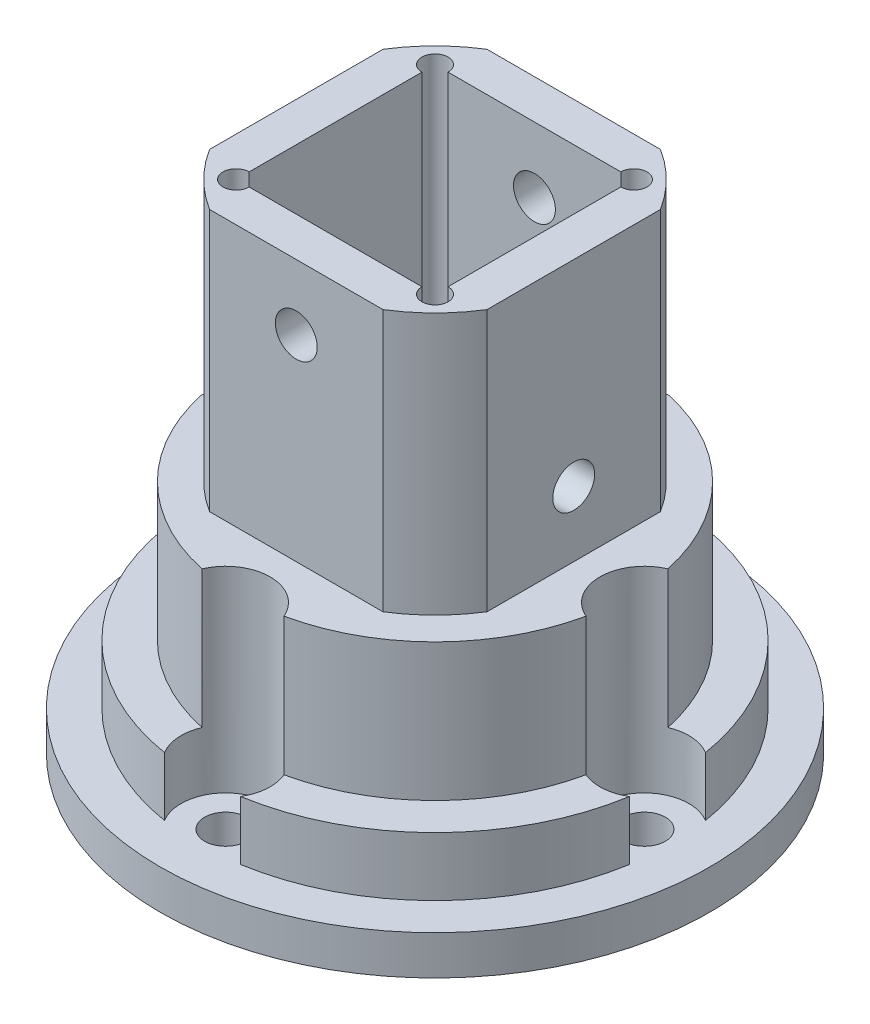
SolidWorks part; units mm, degrees
ref_plane "前视基准面" through (0, 0, 0) normal (0, 0, 1) x (1, 0, 0)
ref_plane "上视基准面" through (0, 0, 0) normal (0, 1, 0) x (1, 0, 0)
ref_plane "右视基准面" through (0, 0, 0) normal (1, 0, 0) x (0, 0, -1)
sketch "草图1" plane through (0, 0, 0) normal (0, 1, 0) x (1, 0, 0)
  line L1 (-7.6, -7.6) -> (7.6, -7.6)
  line L2 (-7.6, -7.6) -> (-7.6, 7.6)
  line L3 (-7.6, 7.6) -> (7.6, 7.6)
  line L4 (7.6, -7.6) -> (7.6, 7.6)
  line L5 (-7.6, -7.6) -> (7.6, 7.6) construction
  line L6 (-7.6, 7.6) -> (7.6, -7.6) construction
  circle A0 centre (0, 0) radius 12.5
  circle A1 centre (7.6, 7.6) radius 1
  circle A2 centre (7.6, -7.6) radius 1
  circle A3 centre (-7.6, -7.6) radius 1
  circle A4 centre (-7.6, 7.6) radius 1
  point P0 (0, 0)
  dimension "D3" = 25
  dimension "D4" = 2
  dimension "D5" = 2
  dimension "D6" = 2
  dimension "D7" = 2
  dimension "D1" = 15.2
  dimension "D2" = 15.2
extrude "凸台-拉伸1" add sketch "草图1" along normal mid plane 15 contours A0 A4 L3 A1 L4 A2 L1 A3 L2 region at (-12.1464, 0, 0)
sketch "草图2" plane through (0, -7.5, 0) normal (0, -1, 0) x (1, 0, 0)
  line L1 (-10.6, -10.6) -> (10.6, -10.6)
  line L2 (-10.6, -10.6) -> (-10.6, 10.6)
  line L3 (-10.6, 10.6) -> (10.6, 10.6)
  line L4 (10.6, -10.6) -> (10.6, 10.6)
  line L5 (-10.6, -10.6) -> (10.6, 10.6) construction
  line L6 (-10.6, 10.6) -> (10.6, -10.6) construction
  line L7 (-7.6, -7.6) -> (7.6, -7.6)
  line L8 (-7.6, -7.6) -> (-7.6, 7.6)
  line L9 (-7.6, 7.6) -> (7.6, 7.6)
  line L10 (7.6, -7.6) -> (7.6, 7.6)
  line L11 (-7.6, -7.6) -> (7.6, 7.6) construction
  line L12 (-7.6, 7.6) -> (7.6, -7.6) construction
  circle A1 centre (7.6, 7.6) radius 1
  circle A2 centre (-7.6, 7.6) radius 1
  circle A3 centre (-7.6, -7.6) radius 1
  circle A4 centre (7.6, -7.6) radius 1
  point P0 (0, 0)
  point P8 (0, 0)
  arc M9 (-6.6, -7.6) -> (-7.6, -6.6) centre (-7.6, -7.6) cw
  line M10 (-7.6, -6.6) -> (-7.6, 6.6)
  arc M11 (-7.6, 6.6) -> (-6.6, 7.6) centre (-7.6, 7.6) cw
  line M12 (-6.6, 7.6) -> (6.6, 7.6)
  arc M13 (6.6, 7.6) -> (7.6, 6.6) centre (7.6, 7.6) cw
  line M14 (7.6, 6.6) -> (7.6, -6.6)
  arc M15 (7.6, -6.6) -> (6.6, -7.6) centre (7.6, -7.6) cw
  line M16 (6.6, -7.6) -> (-6.6, -7.6)
  circle M17 centre (0, 0) radius 12.5
  dimension "D5" = 2
  dimension "D6" = 2
  dimension "D7" = 2
  dimension "D8" = 2
  dimension "D1" = 15.2
  dimension "D2" = 15.2
  dimension "D3" = 3
  dimension "D4" = 3
extrude "凸台-拉伸2" add sketch "草图2" along normal blind 10 contours L4 L3 L2 L1 M17 M16 M9 M10 M11 M12 M13 M14 M15 region at (-8.6268, -7.5, -8.6268)
mirror "镜向1" about plane through (0, 0, 0) normal (0, 1, 0) of "凸台-拉伸2"
sketch "草图3" plane through (0, -7.5, 0) normal (0, -1, 0) x (1, 0, 0)
  circle A0 centre (0, 0) radius 18
  circle A1 centre (0, 0) radius 12.5
  dimension "D1" = 36
  dimension "D2" = 25
extrude "凸台-拉伸3" add sketch "草图3" against normal blind 4.5
sketch "草图4" plane through (0, 0, 10.6) normal (0, 0, 1) x (1, 0, 0)
  line L0 (-6.625, -12.5) -> (6.625, -12.5) construction
  line L1 (-6.625, -17.5) -> (-6.625, -7.5) construction
  line L2 (6.625, -17.5) -> (6.625, -7.5) construction
  line L3 (0, 0) -> (0, -12.5) construction
  circle A0 centre (0, -12.5) radius 2.1
  dimension "D1" = 4.2
extrude "切除-拉伸1" cut sketch "草图4" against normal through all
sketch "草图5" plane through (10.6, 0, 0) normal (1, 0, 0) x (0, 0, -1)
  line L0 (-6.625, 12.5) -> (6.625, 12.5) construction
  line L1 (-6.625, 17.5) -> (-6.625, 7.5) construction
  line L2 (6.625, 17.5) -> (6.625, 7.5) construction
  circle A0 centre (0, 12.5) radius 1.6
  dimension "D1" = 3.2
extrude "切除-拉伸2" cut sketch "草图5" against normal through all
sketch "草图6" plane through (0, -17.5, 0) normal (0, -1, 0) x (1, 0, 0)
  line L4 (10.6, -6.625) -> (10.6, 6.625)
  line L5 (6.625, 10.6) -> (-6.625, 10.6)
  line L6 (-10.6, 6.625) -> (-10.6, -6.625)
  line L7 (-6.625, -10.6) -> (6.625, -10.6)
  line L8 (10.6, -6.625) -> (10.6, 6.625)
  line L9 (6.625, 10.6) -> (-6.625, 10.6)
  line L10 (-10.6, 6.625) -> (-10.6, -6.625)
  line L11 (-6.625, -10.6) -> (6.625, -10.6)
  arc A4 (6.625, -10.6) -> (10.6, -6.625) centre (0, 0) ccw
  arc A5 (10.6, 6.625) -> (6.625, 10.6) centre (0, 0) ccw
  arc A6 (-6.625, 10.6) -> (-10.6, 6.625) centre (0, 0) ccw
  arc A7 (-10.6, -6.625) -> (-6.625, -10.6) centre (0, 0) ccw
  arc A8 (6.625, -10.6) -> (10.6, -6.625) centre (0, 0) ccw
  arc A9 (10.6, 6.625) -> (6.625, 10.6) centre (0, 0) ccw
  arc A10 (-6.625, 10.6) -> (-10.6, 6.625) centre (0, 0) ccw
  arc A11 (-10.6, -6.625) -> (-6.625, -10.6) centre (0, 0) ccw
  dimension "D1" = 0
extrude "切除-拉伸3" cut sketch "草图6" against normal blind 10
sketch "草图7" plane through (0, -7.5, 0) normal (0, -1, 0) x (1, 0, 0)
  circle A0 centre (0, 0) radius 21
  dimension "D1" = 42
extrude "凸台-拉伸4" add sketch "草图7" along normal blind 3
sketch "草图8" plane through (0, -10.5, 0) normal (0, -1, 0) x (1, 0, 0)
  circle A0 centre (0, 0) radius 16 construction
  circle A1 centre (0, 16) radius 1.6
  circle A2 centre (16, 0) radius 1.6
  circle A3 centre (0, -16) radius 1.6
  circle A4 centre (-16, 0) radius 1.6
  point P14 (0, 0)
  dimension "D1" = 32
  dimension "D2" = 3.2
  dimension "D3" = 4
extrude "切除-拉伸4" cut sketch "草图8" against normal through all
sketch "草图13" plane through (0, -3, 0) normal (0, 1, 0) x (1, 0, 0)
  circle A0 centre (0, 0) radius 12.5
  circle A1 centre (0, 0) radius 15
  dimension "D1" = 30
extrude "凸台-拉伸6" add sketch "草图13" along normal up to surface (10.5 mm away) up to face at (0, 7.5, 11.55)
sketch "草图10" plane through (0, -7.5, 0) normal (0, 1, 0) x (1, 0, 0)
  line L4 (-7.6, 6.6) -> (-7.6, -6.6)
  line L5 (-6.6, -7.6) -> (6.6, -7.6)
  line L6 (7.6, -6.6) -> (7.6, 6.6)
  line L7 (6.6, 7.6) -> (-6.6, 7.6)
  line L8 (-7.6, 6.6) -> (-7.6, -6.6)
  line L9 (-6.6, -7.6) -> (6.6, -7.6)
  line L10 (7.6, -6.6) -> (7.6, 6.6)
  line L11 (6.6, 7.6) -> (-6.6, 7.6)
  arc A4 (-6.6, 7.6) -> (-7.6, 6.6) centre (-7.6, 7.6) ccw
  arc A5 (-7.6, -6.6) -> (-6.6, -7.6) centre (-7.6, -7.6) ccw
  arc A6 (6.6, -7.6) -> (7.6, -6.6) centre (7.6, -7.6) ccw
  arc A7 (7.6, 6.6) -> (6.6, 7.6) centre (7.6, 7.6) ccw
  arc A8 (-6.6, 7.6) -> (-7.6, 6.6) centre (-7.6, 7.6) ccw
  arc A9 (-7.6, -6.6) -> (-6.6, -7.6) centre (-7.6, -7.6) ccw
  arc A10 (6.6, -7.6) -> (7.6, -6.6) centre (7.6, -7.6) ccw
  arc A11 (7.6, 6.6) -> (6.6, 7.6) centre (7.6, 7.6) ccw
  dimension "D1" = 0
extrude "切除-拉伸6" cut sketch "草图10" against normal through all and the other way through all
sketch "草图9" plane through (0, -3, 0) normal (0, 1, 0) x (1, 0, 0)
  circle A0 centre (0, -16) radius 3.4
  circle A1 centre (16, 0) radius 3.4
  circle A2 centre (0, 16) radius 3.4
  circle A3 centre (-16, 0) radius 3.4
  dimension "D1" = 6.8
  dimension "D2" = 6.8
  dimension "D3" = 6.8
  dimension "D4" = 6.8
extrude "切除-拉伸5" cut sketch "草图9" against normal up to surface (4.5 mm away) from surface up to face at (0, -7.5, -18) starting at face at (0, 7.5, 0)
sketch "草图11" plane through (0, 17.5, 0) normal (0, 1, 0) x (1, 0, 0)
  line L2 (-6.6, -7.6) -> (6.6, -7.6) construction
  line L3 (-6.6, -7.6) -> (6.6, -7.6)
  line L4 (6.625, 10.6) -> (-6.625, 10.6)
  line L5 (-10.6, 6.625) -> (-10.6, -6.625)
  line L6 (-6.625, -10.6) -> (6.625, -10.6)
  line L7 (10.6, -6.625) -> (10.6, 6.625)
  line L8 (6.625, 10.6) -> (-6.625, 10.6)
  line L9 (-10.6, 6.625) -> (-10.6, -6.625)
  line L10 (-6.625, -10.6) -> (6.625, -10.6)
  line L11 (10.6, -6.625) -> (10.6, 6.625)
  line L12 (7.6, -6.6) -> (7.6, 6.6) construction
  line L13 (6.6, 7.6) -> (-6.6, 7.6) construction
  line L14 (-7.6, 6.6) -> (-7.6, -6.6) construction
  line L15 (7.6, -6.6) -> (7.6, 6.6)
  line L16 (6.6, 7.6) -> (-6.6, 7.6)
  line L17 (-7.6, 6.6) -> (-7.6, -6.6)
  arc A1 (6.6, -7.6) -> (7.6, -6.6) centre (7.6, -7.6) ccw construction
  arc A2 (7.6, 6.6) -> (6.6, 7.6) centre (7.6, 7.6) ccw construction
  arc A3 (-6.6, 7.6) -> (-7.6, 6.6) centre (-7.6, 7.6) ccw construction
  arc A4 (10.6, 6.625) -> (6.625, 10.6) centre (0, 0) ccw
  arc A5 (-6.625, 10.6) -> (-10.6, 6.625) centre (0, 0) ccw
  arc A6 (-10.6, -6.625) -> (-6.625, -10.6) centre (0, 0) ccw
  arc A7 (6.625, -10.6) -> (10.6, -6.625) centre (0, 0) ccw
  arc A8 (10.6, 6.625) -> (6.625, 10.6) centre (0, 0) ccw
  arc A9 (-6.625, 10.6) -> (-10.6, 6.625) centre (0, 0) ccw
  arc A10 (-10.6, -6.625) -> (-6.625, -10.6) centre (0, 0) ccw
  arc A11 (6.625, -10.6) -> (10.6, -6.625) centre (0, 0) ccw
  arc A12 (-7.6, -6.6) -> (-6.6, -7.6) centre (-7.6, -7.6) ccw construction
  arc A13 (6.6, -7.6) -> (7.6, -6.6) centre (7.6, -7.6) ccw
  arc A14 (7.6, 6.6) -> (6.6, 7.6) centre (7.6, 7.6) ccw
  arc A15 (-6.6, 7.6) -> (-7.6, 6.6) centre (-7.6, 7.6) ccw
  arc A16 (-7.6, -6.6) -> (-6.6, -7.6) centre (-7.6, -7.6) ccw
  dimension "D1" = 0
extrude "凸台-拉伸5" add sketch "草图11" along normal blind 10
sketch "草图12" plane through (0, 0, -10.6) normal (0, 0, -1) x (-1, 0, 0)
  line L0 (0, 27.5) -> (0, 0) construction
  line L1 (-6.625, 27.5) -> (6.625, 27.5) construction
  circle A0 centre (0, 22.5) radius 1.6
  dimension "D1" = 3.2
  dimension "D2" = 5
extrude "切除-拉伸7" cut sketch "草图12" against normal through all
